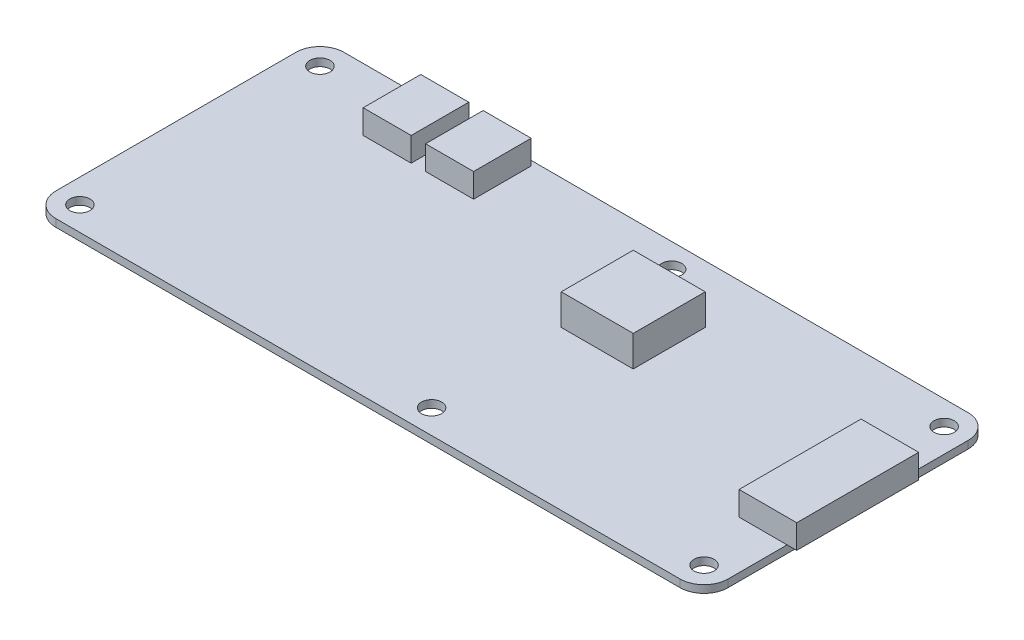
SolidWorks part; units mm, degrees
ref_plane "Front Plane" through (0, 0, 0) normal (0, 0, 1) x (1, 0, 0)
ref_plane "Top Plane" through (0, 0, 0) normal (0, 1, 0) x (1, 0, 0)
ref_plane "Right Plane" through (0, 0, 0) normal (1, 0, 0) x (0, 0, -1)
sketch "Sketch2" plane through (0, 0, 0) normal (0, 1, 0) x (1, 0, 0)
  line L0 (0, 55) -> (140, 55) construction
  line L1 (5, 0) -> (135, 0)
  line L2 (0, 5) -> (0, 55)
  line L3 (5, 60) -> (135, 60)
  line L4 (140, 5) -> (140, 55)
  line L5 (140, 5) -> (0, 5) construction
  arc A0 (0, 5) -> (5, 0) centre (5, 5) ccw
  arc A1 (140, 55) -> (135, 60) centre (135, 55) ccw
  arc A2 (135, 0) -> (140, 5) centre (135, 5) ccw
  arc A3 (5, 60) -> (0, 55) centre (5, 55) ccw
  circle A4 centre (5, 55) radius 2.1
  circle A5 centre (5, 5) radius 2.1
  circle A6 centre (135, 5) radius 2.1
  circle A7 centre (135, 55) radius 2.1
  circle A8 centre (78.25, 55) radius 2.1
  circle A9 centre (78.25, 5) radius 2.1
  point P7 (0, 0)
  point P10 (140, 60)
  point P15 (0, 60)
  dimension "D3" = 5
  dimension "D5" = 4.2
  dimension "D1" = 60
  dimension "D2" = 140
  dimension "D4" = 78.25
extrude "Boss-Extrude1" add sketch "Sketch2" along normal blind 1.5748
sketch "Sketch3" plane through (0, 1.5748, 0) normal (0, 1, 0) x (1, 0, 0)
  line L0 (140, 30) -> (142, 30) construction
  line L1 (130, 42.7) -> (142, 42.7)
  line L2 (130, 42.7) -> (130, 17.3)
  line L3 (130, 17.3) -> (142, 17.3)
  line L4 (142, 42.7) -> (142, 17.3)
  line L5 (0, 55) -> (0, 5) construction
  line L6 (140, 5) -> (140, 55) construction
  line L7 (35, 59) -> (45, 59)
  line L8 (22, 59) -> (32, 59)
  line L9 (22, 59) -> (22, 47)
  line L10 (22, 47) -> (32, 47)
  line L11 (32, 59) -> (32, 47)
  line L12 (35, 59) -> (35, 47)
  line L13 (35, 47) -> (45, 47)
  line L14 (45, 59) -> (45, 47)
  line L15 (135, 60) -> (5, 60) construction
  dimension "D1" = 2
  dimension "D2" = 25.4
  dimension "D3" = 12
  dimension "D4" = 22
  dimension "D5" = 3
  dimension "D6" = 1
  dimension "D7" = 12
  dimension "D8" = 10
extrude "Boss-Extrude2" add sketch "Sketch3" along normal blind 5 contours L4 L3 L2 L1 | L9 L8 L11 L10 | L12 L7 L14 L13
sketch "Sketch5" plane through (0, 1.5748, 0) normal (0, 1, 0) x (1, 0, 0)
  line L0 (135, 60) -> (5, 60) construction
  line L1 (77.25, 48) -> (92.25, 48)
  line L2 (77.25, 48) -> (77.25, 33)
  line L3 (77.25, 33) -> (92.25, 33)
  line L4 (92.25, 48) -> (92.25, 33)
  circle A1 centre (78.25, 55) radius 2.1 construction
  dimension "D1" = 12
  dimension "D2" = 15
  dimension "D3" = 1
extrude "Boss-Extrude3" add sketch "Sketch5" along normal offset from surface (6.4252 mm away) 8 up to face at (70, 0, -30) offset beyond the face yes
